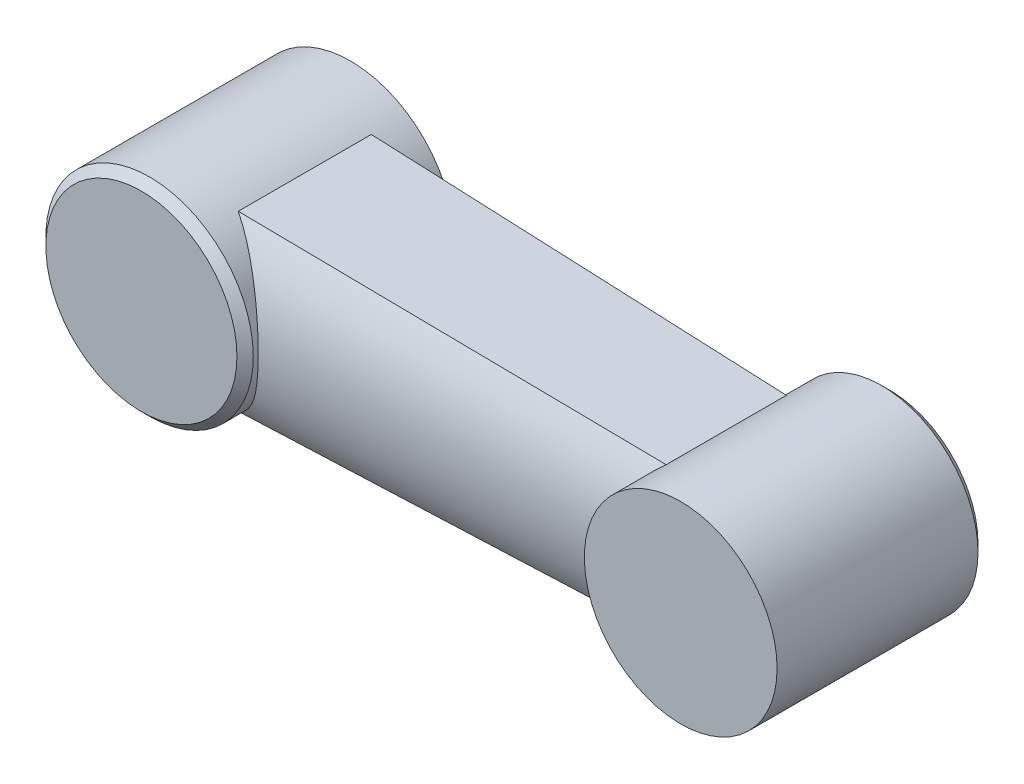
SolidWorks part; units mm, degrees
ref_plane "Front Plane" through (0, 0, 0) normal (0, 0, 1) x (1, 0, 0)
ref_plane "Top Plane" through (0, 0, 0) normal (0, 1, 0) x (1, 0, 0)
ref_plane "Right Plane" through (0, 0, 0) normal (1, 0, 0) x (0, 0, -1)
sketch "Sketch1" plane through (0, 0, 0) normal (0, 0, 1) x (1, 0, 0)
  circle A0 centre (0, 0) radius 63.5
  dimension "D1" = 127
extrude "Boss-Extrude1" add sketch "Sketch1" along normal blind 64 and the other way blind 64
chamfer "Chamfer1" distance 5 angle 45 1 edges at (63.5, 0, 64)
ref_plane "Plane2" through (63.5, 0, 0) normal (1, 0, 0) x (0, 0, -1)
ref_plane "Plane1" through (271.2, 0, 0) normal (1, 0, 0) x (0, 0, -1)
ref_plane "Plane3" through (330.2, 0, 0) normal (1, 0, 0) x (0, 0, -1)
ref_plane "Plane4" through (0, 0, 0) normal (0, 0, 1) x (1, 0, 0)
sketch "Sketch6" plane through (0, 0, 0) normal (-1, 0, 0) x (0, 0, 1)
  line L0 (-57.7088, 0) -> (57.7088, 0) construction
  line L6 (40.1204, -54) -> (-42.3796, -54)
  line L7 (-42.3796, 54) -> (40.1204, 54)
  arc A5 (-42.3796, 54) -> (-42.3796, -54) centre (45.0683, 0) ccw
  arc A6 (40.1204, 54) -> (40.1204, -54) centre (-33.9807, 0) cw
sketch "Sketch7" plane through (330.2, 0, 59) normal (-1, 0, 0) x (0, 0, 1)
  line L7 (-23.6711, -44.884) -> (-96.1377, -44.884)
  line L8 (-96.1377, 44.884) -> (-23.6711, 44.884)
  line L9 (-107.5928, 0) -> (-10.4072, 0) construction
  arc A11 (-96.1377, 44.884) -> (-96.1377, -44.884) centre (-13.9317, 0) ccw
  arc A12 (-23.6711, 44.884) -> (-23.6711, -44.884) centre (-92.9807, 0) cw
loft "Loft1" add profiles "Sketch6", "Sketch7" start constraint default end constraint default
sketch "Sketch9" plane through (0, 0, 0) normal (0, 0, 1) x (1, 0, 0)
  line L0 (330.2, -44.884) -> (330.2, 44.884) construction
  circle A0 centre (330.2, 0) radius 59
  dimension "D1" = 118
extrude "Boss-Extrude2" add sketch "Sketch9" along normal blind 64 and the other way blind 64
chamfer "Chamfer2" distance 5 angle 45 1 edges at (389.2, 0, -64)
ref_axis "Axis1" through (0, 0, 59) along (0, 0, -1)
ref_point "Point1"
